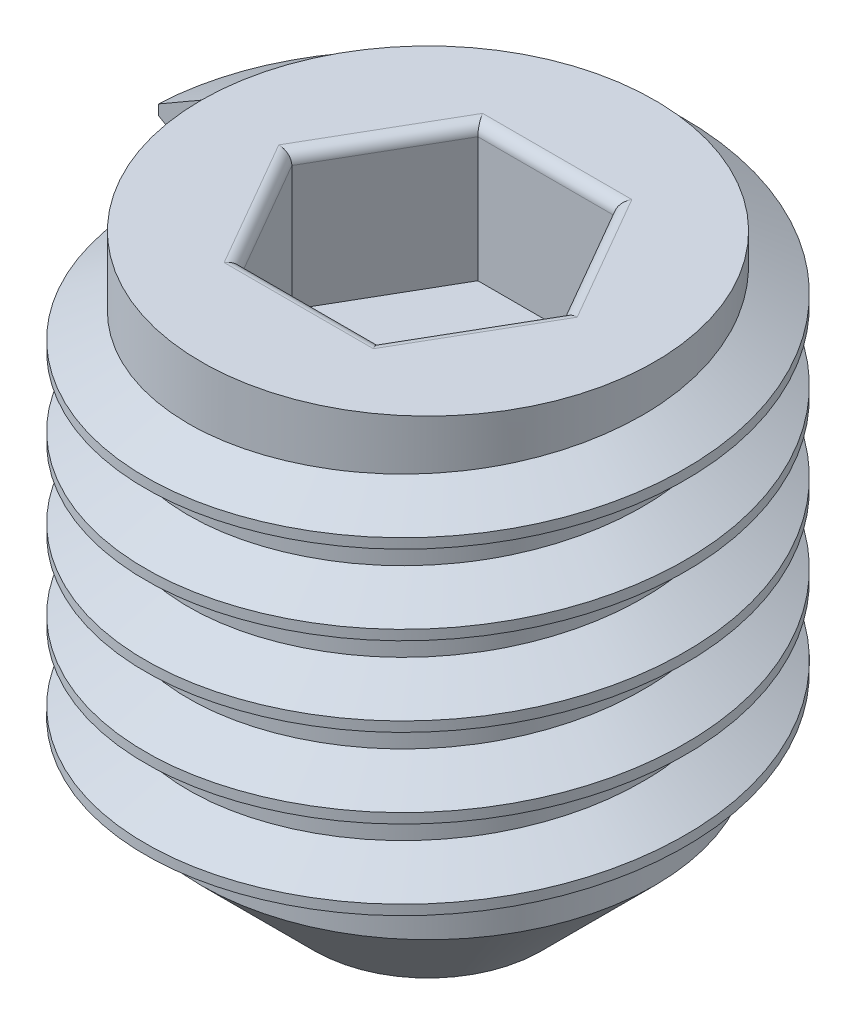
SolidWorks part; units mm, degrees
ref_plane "Front Plane" through (0, 0, 0) normal (0, 0, 1) x (1, 0, 0)
ref_plane "Top Plane" through (0, 0, 0) normal (0, 1, 0) x (1, 0, 0)
ref_plane "Right Plane" through (0, 0, 0) normal (1, 0, 0) x (0, 0, -1)
sketch "Sketch1" plane through (0, 0, 0) normal (0, 1, 0) x (1, 0, 0)
  circle A0 centre (0, 0) radius 2
  dimension "D1" = 4
extrude "Boss-Extrude1" add sketch "Sketch1" along normal blind 5
chamfer "Chamfer1" distance 1 angle 45 1 edges at (0, 0, 2)
thread "Thread1" pitch 0.7 method extrude profile "Thread Profile1" start angle 0, offset 0, length 3.5, pitch 0.7, diameter 4
ref_plane "Plane1" through (-2, 5, 0) normal (0, 0, 1) x (-1, 0, 0)
sketch "Thread Profile1" plane through (-2, 5, 0) normal (0, 0, 1) x (-1, 0, 0)
  line L0 (0, 0) -> (0, 0.7) construction
  line L1 (0, 0) -> (0.3789, 0.2187)
  line L2 (0.3789, 0.2187) -> (0.3789, 0.3062)
  line L3 (0.3789, 0.3062) -> (0, 0.525)
  line L4 (0.3789, 0.2625) -> (0, 0.2625) construction
  line L11 (0, 0) -> (0, 0.525)
  point P2 (0, 0)
  dimension "Pitch" = 0.7
  dimension "Profile_Angle" = 60
  dimension "Profile_Land" = 0.0875
  dimension "Profile_Height" = 0.3789
sketch "Sketch6" plane through (0, 5, 0) normal (0, 1, 0) x (1, 0, 0)
  line L1 (0.6004, 1.04) -> (-0.6004, 1.04)
  line L2 (-0.6004, 1.04) -> (-1.2009, 0)
  line L3 (-1.2009, 0) -> (-0.6004, -1.04)
  line L4 (-0.6004, -1.04) -> (0.6004, -1.04)
  line L5 (0.6004, -1.04) -> (1.2009, 0)
  line L6 (1.2009, 0) -> (0.6004, 1.04)
  circle A0 centre (0, 0) radius 1.04 construction
  dimension "D1" = 2.08
extrude "Cut-Extrude1" cut sketch "Sketch6" against normal blind 1.2
fillet "Fillet1" radius 0.1 6 edges at (0, 5, 1.04) (-0.9007, 5, 0.52) (-0.9007, 5, -0.52) (0, 5, -1.04) (0.9007, 5, -0.52) (0.9007, 5, 0.52)
